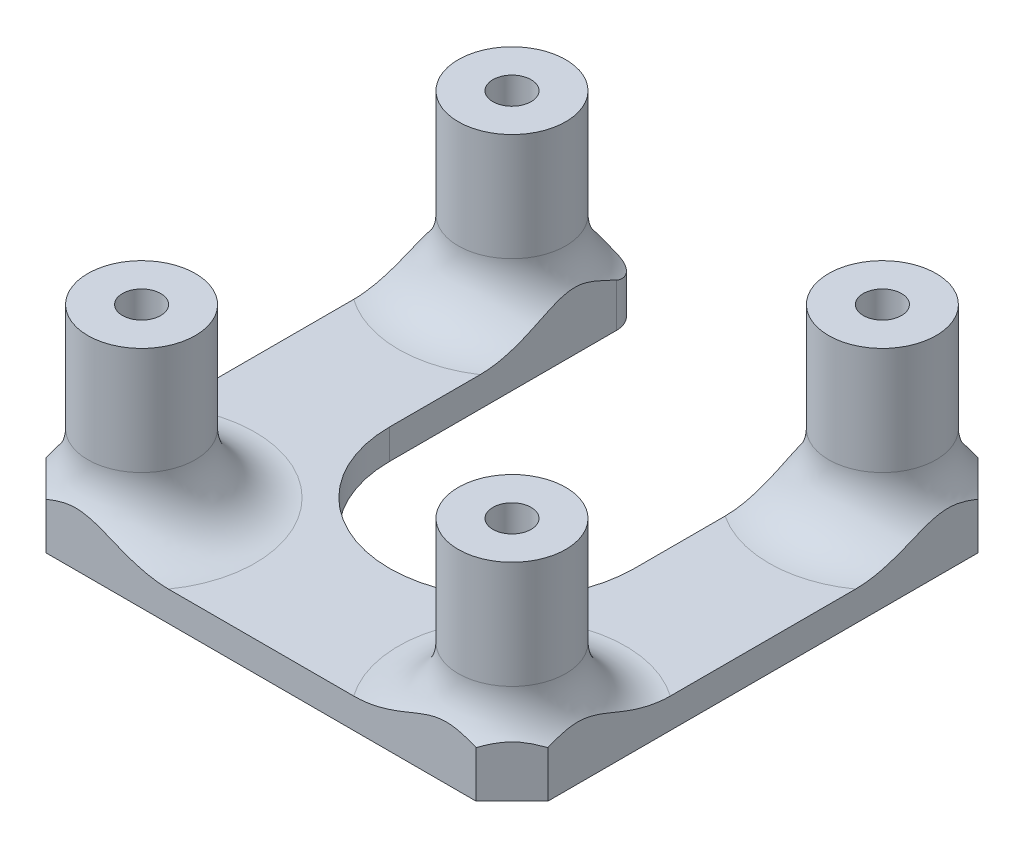
SolidWorks part; units mm, degrees
ref_plane "Alzado" through (0, 0, 0) normal (0, 0, 1) x (1, 0, 0)
ref_plane "Planta" through (0, 0, 0) normal (0, 1, 0) x (1, 0, 0)
ref_plane "Vista lateral" through (0, 0, 0) normal (1, 0, 0) x (0, 0, -1)
sketch "Croquis1" plane through (0, 0, 0) normal (0, 1, 0) x (1, 0, 0)
  line L0 (-10.25, 0) -> (-10.25, 21)
  line L1 (-21, -21) -> (21, -21)
  line L2 (-21, -21) -> (-21, 21)
  line L3 (-21, 21) -> (-10.25, 21)
  line L4 (21, -21) -> (21, 21)
  line L5 (-21, -21) -> (21, 21) construction
  line L6 (-21, 21) -> (21, -21) construction
  line L7 (-15.5, -15.5) -> (15.5, -15.5) construction
  line L8 (-15.5, -15.5) -> (-15.5, 15.5) construction
  line L9 (-15.5, 15.5) -> (15.5, 15.5) construction
  line L10 (15.5, -15.5) -> (15.5, 15.5) construction
  line L11 (-15.5, -15.5) -> (15.5, 15.5) construction
  line L12 (-15.5, 15.5) -> (15.5, -15.5) construction
  line L13 (10.25, 0) -> (10.25, 21)
  line L14 (10.25, 21) -> (21, 21)
  circle A0 centre (-15.5, 15.5) radius 1.6
  circle A1 centre (15.5, 15.5) radius 1.6
  circle A2 centre (15.5, -15.5) radius 1.6
  circle A3 centre (-15.5, -15.5) radius 1.6
  arc A4 (-10.25, 0) -> (10.25, 0) centre (0, 0) ccw
  point P0 (0, 0)
  point P6 (0, 0)
  dimension "D5" = 3.2
  dimension "D6" = 20.5
  dimension "D1" = 42
  dimension "D2" = 42
  dimension "D3" = 31
  dimension "D4" = 31
extrude "Saliente-Extruir1" add sketch "Croquis1" along normal blind 2.5
chamfer "Chaflán1" distance 3 angle 45 4 edges at (-21, 1.25, 21) (21, 1.25, 21) (-21, 1.25, -21) (21, 1.25, -21)
fillet "Redondeo1" radius 2 2 edges at (10.25, 1.25, -21) (-10.25, 1.25, -21)
sketch "Croquis2" plane through (0, 2.5, 0) normal (0, 1, 0) x (1, 0, 0)
  circle A0 centre (-15.5, 15.5) radius 4.5
  circle A1 centre (15.5, 15.5) radius 4.5
  circle A2 centre (15.5, -15.5) radius 4.5
  circle A3 centre (-15.5, -15.5) radius 4.5
  circle A4 centre (-15.5, -15.5) radius 1.6 construction
  circle A5 centre (15.5, -15.5) radius 1.6 construction
  circle A6 centre (15.5, 15.5) radius 1.6 construction
  circle A7 centre (-15.5, 15.5) radius 1.6 construction
  circle A8 centre (-15.5, -15.5) radius 1.6
  circle A9 centre (15.5, -15.5) radius 1.6
  circle A10 centre (15.5, 15.5) radius 1.6
  circle A11 centre (-15.5, 15.5) radius 1.6
  dimension "D1" = 9
extrude "Saliente-Extruir2" add sketch "Croquis2" along normal blind 14
fillet "Redondeo2" radius 5 4 edges at (-15.5, 2.5, 20) (15.5, 2.5, 20) (15.5, 2.5, -11) (-15.5, 2.5, -11)
